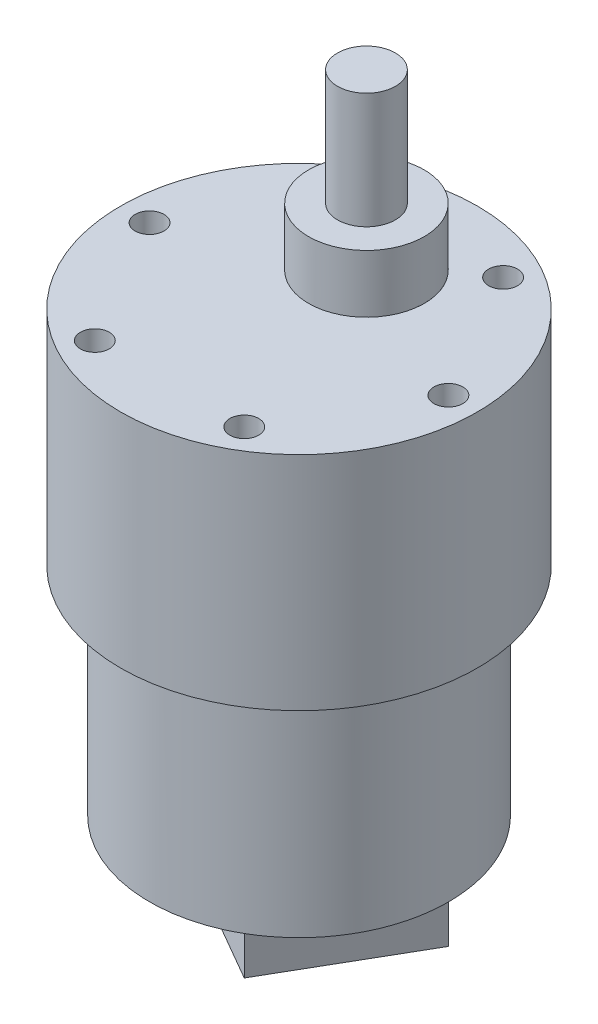
SolidWorks part; units mm, degrees
ref_plane "前视基准面" through (0, 0, 0) normal (0, 0, 1) x (1, 0, 0)
ref_plane "上视基准面" through (0, 0, 0) normal (0, 1, 0) x (1, 0, 0)
ref_plane "右视基准面" through (0, 0, 0) normal (1, 0, 0) x (0, 0, -1)
sketch "草图1" plane through (0, 0, 0) normal (0, 1, 0) x (1, 0, 0)
  line L0 (2, 0) -> (-13.4965, 0) construction
  circle A0 centre (2.0035, 0) radius 18.5
  circle A2 centre (-13.4965, 0) radius 1.5
  circle A3 centre (2.0035, 7) radius 6
  circle A6 centre (-5.7483, 13.4204) radius 1.5
  circle A7 centre (9.7483, 13.4204) radius 1.5
  circle A8 centre (17.4965, 0) radius 1.5
  circle A9 centre (9.7483, -13.4204) radius 1.5
  circle A10 centre (-5.7483, -13.4204) radius 1.5
  dimension "D1" = 15.4965
extrude "凸台-拉伸1" add sketch "草图1" along normal blind 23
sketch "草图2" plane through (0, 23, 0) normal (0, 1, 0) x (1, 0, 0)
  circle A0 centre (2.0004, 6.9946) radius 6
extrude "凸台-拉伸2" add sketch "草图2" along normal blind 6
sketch "草图4" plane through (0, 29, 0) normal (0, 1, 0) x (1, 0, 0)
  circle A1 centre (2.0032, 6.9966) radius 3
extrude "凸台-拉伸3" add sketch "草图4" along normal blind 12
sketch "草图5" plane through (0, 0, 0) normal (0, -1, 0) x (1, 0, 0)
  circle A1 centre (2.0035, 0) radius 15.5
extrude "凸台-拉伸4" add sketch "草图5" along normal blind 22.5
sketch "草图6" plane through (0, -22.5, 0) normal (0, -1, 0) x (1, 0, 0)
  circle A1 centre (2.0035, 0) radius 5.5
  point P2 (0, 0)
  point P3 (1.0961, -4.9411)
  point P4 (-6.9243, -5.514)
  point P5 (2.0035, 0)
  dimension "D1" = 11
extrude "凸台-拉伸5" add sketch "草图6" along normal blind 3
sketch "草图7" plane through (0, -22.5, 0) normal (0, -1, 0) x (1, 0, 0)
  line L0 (9.7483, 13.4204) -> (17.4965, 0)
  line L1 (17.4965, 0) -> (11.9516, -3.2013)
  line L2 (11.9516, -3.2013) -> (4.2034, 10.219)
  line L3 (4.2034, 10.219) -> (9.7483, 13.4204)
extrude "凸台-拉伸6" add sketch "草图7" along normal blind 4
